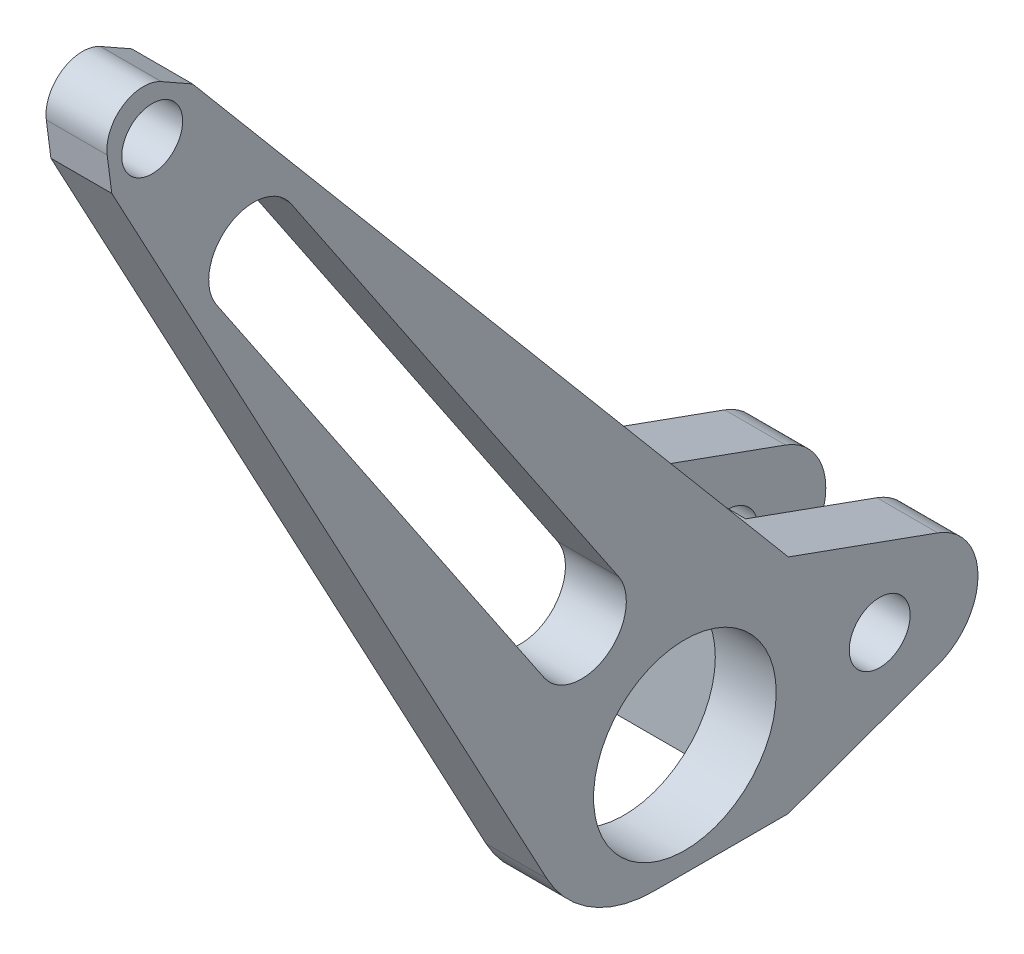
SolidWorks part; units mm, degrees
ref_plane "前视基准面" through (0, 0, 0) normal (0, 0, 1) x (1, 0, 0)
ref_plane "上视基准面" through (0, 0, 0) normal (0, 1, 0) x (1, 0, 0)
ref_plane "右视基准面" through (0, 0, 0) normal (1, 0, 0) x (0, 0, -1)
sketch "草图1" plane through (0, 0, 0) normal (1, 0, 0) x (0, 0, -1)
  line L0 (0, 0) -> (0, 145) construction
  line L1 (0, 0) -> (-100, 0) construction
  line L2 (-87.5, 0) -> (-87.5, 145) construction
  line L3 (-87.5, 145) -> (0, 145) construction
  line L4 (-87.5, 130) -> (0, 0) construction
  line L7 (17, -18.2506) -> (-5.0332, -18.2506)
  line L9 (17, 18.2506) -> (-17, -18.2506) construction
  line L10 (17, -18.2506) -> (-17, 18.2506) construction
  line L15 (17, 18.2506) -> (41.5394, 9.4078)
  line L16 (41.5394, -9.4078) -> (17, -18.2506)
  line L17 (-87.5, 130) -> (-94.1367, 125.533) construction
  line L18 (-87.5, 130) -> (-80.8633, 134.467) construction
  line L19 (-17, -18.2506) -> (-94.1367, 125.533) construction
  line L20 (17, 18.2506) -> (-80.8633, 134.467) construction
  line L21 (-87.5, 130) -> (-96.434, 143.2734) construction
  line L22 (-96.434, 143.2734) -> (-80.8633, 134.467) construction
  line L23 (-80.8633, 134.467) -> (-85.9889, 137.3659)
  line L24 (-94.8929, 131.3728) -> (-94.1367, 125.533)
  line L25 (-80.8633, 134.467) -> (17, 18.2506)
  line L26 (-94.1367, 125.533) -> (-22.6572, -7.7055)
  line L27 (-70.8322, 105.2364) -> (-17, 25.2571) construction
  line L28 (-64.7087, 109.358) -> (-10.8765, 29.3787)
  line L29 (-76.9557, 101.1148) -> (-23.1235, 21.1356)
  circle A1 centre (0, 0) radius 15
  circle A2 centre (-87.5, 130) radius 5
  arc A3 (-85.9889, 137.3659) -> (-94.8929, 131.3728) centre (-88.9426, 132.1433) ccw
  arc A4 (41.5394, -9.4078) -> (41.5394, 9.4078) centre (38.1493, 0) ccw
  circle A6 centre (32, 0) radius 5
  arc A8 (-22.6572, -7.7055) -> (-5.0332, -18.2506) centre (-5.0332, 1.7494) ccw
  arc A9 (-64.7087, 109.358) -> (-76.9557, 101.1148) centre (-70.8322, 105.2364) ccw
  arc A10 (-23.1235, 21.1356) -> (-10.8765, 29.3787) centre (-17, 25.2571) ccw
  point P4 (199.5772, 28.6368)
  point P5 (241.7775, 28.6368)
  point P6 (0, 115)
  point P7 (-87.5, 130)
  point P11 (-87.5, 0)
  point P31 (-43.9161, 65.2468)
  dimension "D1" = 6
  dimension "D2" = 10
  dimension "D4" = 20
extrude "凸台-拉伸1" add sketch "草图1" along normal blind 10
sketch "草图2" plane through (0, 0, 0) normal (1, 0, 0) x (0, 0, -1)
  line L0 (17, 18.2506) -> (17, -18.2506)
  line L1 (17, -18.2506) -> (20, -17.1695)
  line L2 (17, -18.2506) -> (41.5394, -9.4078) construction
  line L3 (20, -17.1695) -> (20, 17.1695)
  line L4 (41.5394, 9.4078) -> (17, 18.2506) construction
  line L5 (20, 17.1695) -> (17, 18.2506)
  dimension "D1" = 3
extrude "凸台-拉伸2" add sketch "草图2" against normal blind 25
sketch "草图4" plane through (0, 0, 0) normal (-1, 0, 0) x (0, 0, 1)
  line L3 (-41.5394, -9.4078) -> (-20, -17.1695)
  line L4 (-20, -17.1695) -> (-20, 17.1695)
  line L5 (-20, 17.1695) -> (-41.5394, 9.4078)
  line L6 (-41.5394, -9.4078) -> (-20, -17.1695)
  line L7 (-20, -17.1695) -> (-20, 17.1695)
  line L8 (-20, 17.1695) -> (-41.5394, 9.4078)
  arc A1 (-41.5394, 9.4078) -> (-41.5394, -9.4078) centre (-38.1493, 0) ccw
  arc A2 (-41.5394, 9.4078) -> (-41.5394, -9.4078) centre (-38.1493, 0) ccw
  line M5 (-41.5394, -9.4078) -> (-20, -17.1695)
  line M6 (-20, -17.1695) -> (-20, 17.1695)
  line M7 (-20, 17.1695) -> (-41.5394, 9.4078)
  arc M8 (-41.5394, 9.4078) -> (-41.5394, -9.4078) centre (-38.1493, 0) ccw
  circle M9 centre (-32, 0) radius 5
  dimension "D1" = 0
extrude "凸台-拉伸3" add sketch "草图4" along normal blind 10 from offset 15 contours M8 M5 M6 M7 M9 region at (0, 0, -47.7053)
